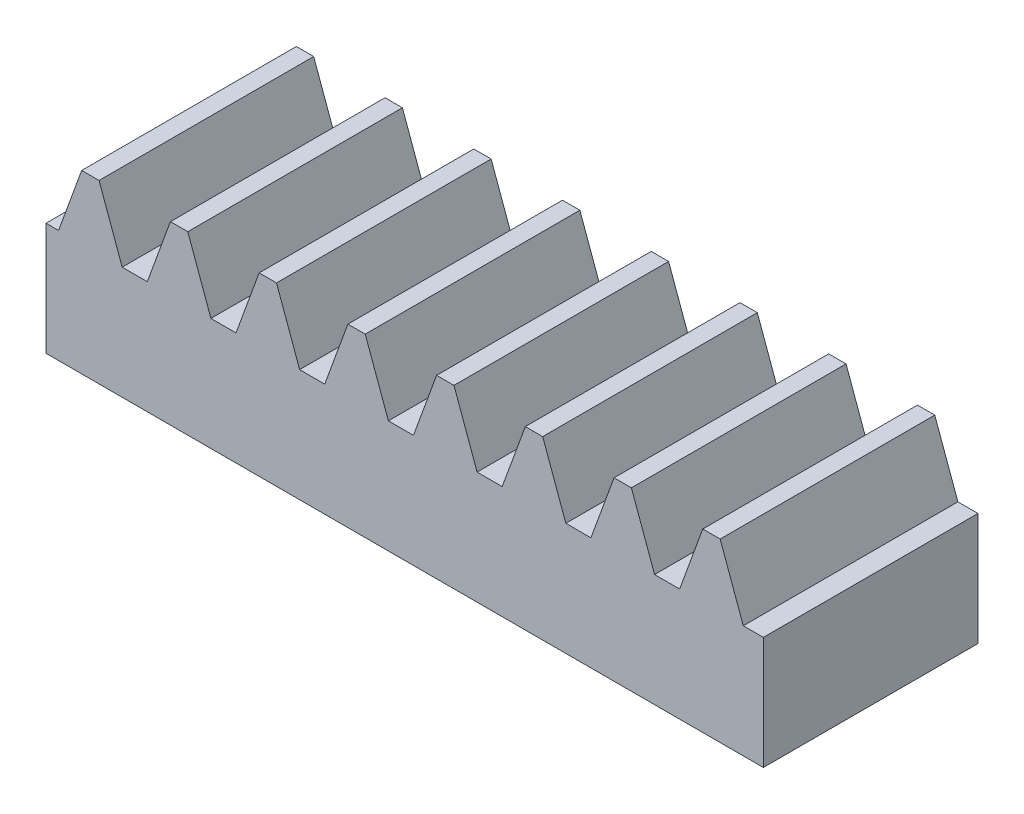
SolidWorks part; units mm, degrees
extrude "Blank" add sketch "BlankSke" against normal blind 3.8
sketch "BlankSke" plane through (0, 0, 0) normal (0, 0, 1) x (1, 0, 0)
  line L1 (0, 0) -> (12.7, 0)
  line L2 (0, 0) -> (0, 3.12)
  line L3 (0, 3.12) -> (12.7, 3.12)
  line L4 (12.7, 0) -> (12.7, 3.12)
  dimension "Length" = 12.7
ref_plane "Plane1" through (0, 0, 0) normal (0, 0, 1) x (1, 0, 0)
ref_plane "Plane2" through (0, 0, 0) normal (0, 1, 0) x (1, 0, 0)
ref_plane "Plane3" through (0, 0, 0) normal (1, 0, 0) x (0, 0, -1)
other "Configuration Table"
sketch "HoldingSke" plane through (0, 0, 0) normal (0, 1, 0) x (1, 0, 0)
  line L0 (0, 0) -> (0.2783, 1.9805)
  line L1 (-15, 0) -> (100, 0) construction
  line L2 (0, 0) -> (-2.1039, 2.3779)
  line L3 (0, 0) -> (-11.863, 4.5341)
  line L4 (0, 0) -> (8.5048, 1.4996)
  line L5 (0, 0) -> (-23.7986, -8.8762)
  line L6 (0, 0) -> (-10.5278, -7.1032)
  line L9 (-71.009, 38.7566) -> (-59.0749, 43.1003)
  line L10 (-76.2, 2.8779) -> (-73.58, 2.8779)
  line L11 (0, 0) -> (-3.8, 0)
  line L12 (-76.2, 101.6) -> (-76.181, 101.6)
  line L13 (24.9733, 27.94) -> (52.9518, 28.4284)
  line L14 (24.9733, 27.94) -> (24.9743, 27.94)
  line L15 (24.9733, 27.94) -> (100.4006, 29.5858)
  circle A0 centre (0, 0) radius 19.05
  circle A1 centre (0, 0) radius 1.31
  circle A2 centre (0, 0) radius 12.7
  dimension "Num_teeth" = 10
  dimension "Width" = 3.8
  dimension "Length" = 12.7
  dimension "Pitch_height" = 2.62
sketch "TooCutSkeIll" plane through (0, 0, 0) normal (0, 0, 1) x (1, 0, 0)
  line L0 (-0.6269, 3.1068) -> (-0.2524, 2.0779)
  line L1 (-0.134, 1.995) -> (0.134, 1.995)
  line L2 (0.2524, 2.0779) -> (0.6269, 3.1068)
  line L3 (12.7, 3.12) -> (0, 3.12) construction
  line L4 (0, 0) -> (0, 64.897) construction
  line L5 (-13.208, 2.62) -> (12.954, 2.62) construction
  line L6 (0, 0) -> (12.7, 0) construction
  line L7 (0.4497, 2.62) -> (0.4497, 48.7463) construction
  line L8 (-0.4497, 2.62) -> (-0.4497, 48.7463) construction
  line L9 (0.6457, 3.12) -> (0.6457, 3.1454)
  line L10 (-0.6457, 3.12) -> (-0.6457, 3.1454)
  line L11 (-0.6457, 3.1454) -> (0.6457, 3.1454)
  arc A0 (0.134, 1.995) -> (0.2524, 2.0779) centre (0.134, 2.121) ccw
  arc A1 (-0.2524, 2.0779) -> (-0.134, 1.995) centre (-0.134, 2.121) ccw
  arc A2 (0.6457, 3.12) -> (0.6269, 3.1068) centre (0.6457, 3.1) ccw
  arc A3 (-0.6269, 3.1068) -> (-0.6457, 3.12) centre (-0.6457, 3.1) ccw
  dimension "Addendum_plus" = 0.5254
  dimension "Pitch_height" = 2.62
  dimension "Pressure_angle" = 20
  dimension "Gap_width" = 0.8994
  dimension "Dedendum" = 0.625
extrude "ToothCutIll" [suppressed] cut sketch "TooCutSkeIll" against normal through all
sketch "TooCutSkeSim" plane through (0, 0, 0) normal (0, 0, 1) x (1, 0, 0)
  line L0 (0.2222, 1.995) -> (-0.2222, 1.995)
  line L1 (0.6409, 3.1454) -> (0.2222, 1.995)
  line L2 (0, 17.4625) -> (0, 53.467) construction
  line L3 (0.6409, 3.1454) -> (-0.6409, 3.1454)
  line L6 (-0.6409, 3.1454) -> (-0.2222, 1.995)
  line L9 (-0.4497, 2.62) -> (0.4497, 2.62) construction
  line L10 (0, 0) -> (12.7, 0) construction
  line L11 (0.4497, 2.62) -> (0.4497, 53.467) construction
  line L12 (-0.4497, 2.62) -> (-0.4497, 53.467) construction
  dimension "Addendum_plus" = 0.5254
  dimension "Pitch_height" = 2.62
  dimension "Pressure_angle" = 20
  dimension "Gap_width" = 0.8994
  dimension "Dedendum" = 0.625
extrude "ToothCutSim" cut sketch "TooCutSkeSim" against normal through all
pattern_linear "TeethCuts" count 10 spacing 1.5708 along (1, 0, 0) of "ToothCutIll", "ToothCutSim"
equation "' \"Module@HoldingSke\" = 6.35"
equation "' \"Num_teeth@HoldingSke\" = 12"
equation "' \"Ap@HoldingSke\" =  20"
equation "' \"Ap@HoldingSke\" = 20"
equation "' \"Width@HoldingSke\" = 0.25 * 25.4"
equation "' \"Show_teeth@HoldingSke\" = 500"
equation "' \"Backlash@HoldingSke\" = 0.009 * 25.4"
equation "' \"Addendum_fac@HoldingSke\" = 1.0"
equation "' \"Dedendum_fac@HoldingSke\" = 1.25"
equation "' \"Dedendum_add@HoldingSke\" = 0.00005 * 25.4"
equation "' \"Clearance_fac@HoldingSke\" = 0.25"
equation "' \"Pitch_height@HoldingSke\" = 1 * 25.4"
equation "' \"Length@HoldingSke\" = 4.71 * 25.4"
equation "\"Pitch@HoldingSke\" = 1 / \"Module@HoldingSke\""
equation "\"MPH@HoldingSke\" = \"Dedendum_fac@HoldingSke\" / \"Pitch@HoldingSke\" + 2 * \"Dedendum_add@HoldingSke\" + 0.002 * 25.4"
equation "\"MPH@HoldingSke\" = ((sgn( \"MPH@HoldingSke\" - \"Pitch_height@HoldingSke\")+1)*( \"MPH@HoldingSke\" - \"Pitch_height@HoldingSke\"))/2 + \"Pitch_height@HoldingSke\""
equation "\"Blank_height@BlankSke\" = \"Pitch_height@HoldingSke\" + \"Addendum_fac@HoldingSke\"  / \"Pitch@HoldingSke\" "
equation "\"Length@BlankSke\" =  \"Length@HoldingSke\""
equation "\"Face_width@Blank\" = \"Width@HoldingSke\""
equation "\"Pressure_angle@TooCutSkeIll\" = \"Ap@HoldingSke\""
equation "\"Addendum_plus@TooCutSkeIll\" =  \"Addendum_fac@HoldingSke\"  / \"Pitch@HoldingSke\" + 0.001 *25.4"
equation "\"Dedendum@TooCutSkeIll\" = \"Dedendum_fac@HoldingSke\"  / \"Pitch@HoldingSke\""
equation "\"Pitch_height@TooCutSkeIll\" =  \"MPH@HoldingSke\""
equation "\"Gap_width@TooCutSkeIll\" = 3.14159265 / 2 / \"Pitch@HoldingSke\" + 6 * \"Backlash@HoldingSke\""
equation "\"Pressure_angle@TooCutSkeSim\" = \"Ap@HoldingSke\""
equation "\"Addendum_plus@TooCutSkeSim\" =  \"Addendum_fac@HoldingSke\"  / \"Pitch@HoldingSke\" + 0.001 * 25.4"
equation "\"Dedendum@TooCutSkeSim\" = \"Dedendum_fac@HoldingSke\"  / \"Pitch@HoldingSke\""
equation "\"Pitch_height@TooCutSkeSim\" =  \"MPH@HoldingSke\""
equation "\"Gap_width@TooCutSkeSim\" = 3.14159265 / 2 / \"Pitch@HoldingSke\" + 6 * \"Backlash@HoldingSke\""
equation "\"Root_fillet@TooCutSkeIll\" = \"Clearance_fac@HoldingSke\" / \"Pitch@HoldingSke\" + \"Dedendum_add@HoldingSke\""
equation "\"Break_rad@TooCutSkeIll\" = 0.02 / \"Pitch@HoldingSke\" * 2"
equation "\"Linear_pitch@TeethCuts\" = 3.14159265 / \"Pitch@HoldingSke\""
equation "\"Num_teeth@HoldingSke\" = int( ( \"Length@HoldingSke\" + 0 ) / (3.14159265 / \"Pitch@HoldingSke\")) + 0.9999  + 1"
equation " \"Num_teeth@TeethCuts\" = int( \"Show_teeth@HoldingSke\" ) + 1"
equation " \"Num_teeth@TeethCuts\" = ((sgn( \"Num_teeth@TeethCuts\" - \"Num_teeth@HoldingSke\" )-1)*( \"Num_teeth@TeethCuts\" - \"Num_teeth@HoldingSke\" ))/-2+ \"Num_teeth@HoldingSke\""
equation " \"Num_teeth@TeethCuts\" = ((sgn( \"Num_teeth@TeethCuts\" - 2.0)+1)*( \"Num_teeth@TeethCuts\" - 2.0))/2 +2.0"
